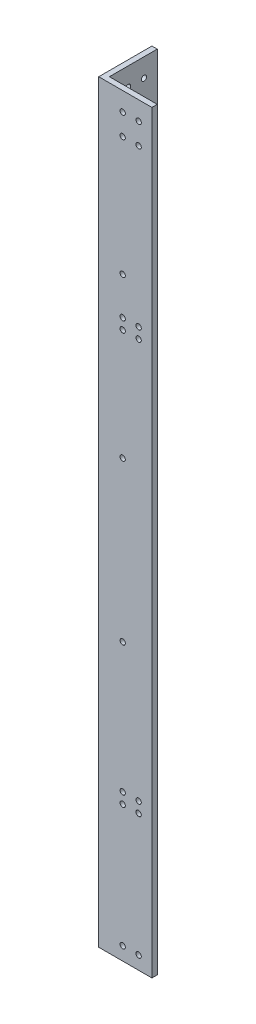
SolidWorks part; units mm, degrees
ref_plane "Front Plane" through (0, 0, 0) normal (0, 0, 1) x (1, 0, 0)
ref_plane "Top Plane" through (0, 0, 0) normal (0, 1, 0) x (1, 0, 0)
ref_plane "Right Plane" through (0, 0, 0) normal (1, 0, 0) x (0, 0, -1)
sketch "Sketch2" plane through (0, 0, 0) normal (0, 1, 0) x (1, 0, 0)
  line L0 (0, 31.75) -> (3.175, 31.75)
  line L1 (3.175, 31.75) -> (3.175, 3.175)
  line L2 (3.175, 3.175) -> (31.75, 3.175)
  line L3 (31.75, 3.175) -> (31.75, 0)
  line L4 (31.75, 0) -> (0, 0)
  line L5 (0, 0) -> (0, 31.75)
  point P9 (1.5875, 31.75)
  point P10 (31.75, 1.5875)
  dimension "D4" = 3.175
  dimension "D1" = 31.75
  dimension "D2" = 31.75
  dimension "D3" = 3.175
extrude "Boss-Extrude1" add sketch "Sketch2" along normal blind 450
sketch "BackSideHoles-Sketch3" plane through (0, 0, 0) normal (0, 0, 1) x (1, 0, 0)
  line L0 (0, 0) -> (31.75, 0) construction
  line L3 (0, 450) -> (0, 0) construction
  circle A0 centre (14.2875, 81.1125) radius 1.5875
  circle A1 centre (23.8125, 81.1125) radius 1.5875
  circle A2 centre (14.2875, 87.4625) radius 1.5875
  circle A3 centre (23.8125, 87.4625) radius 1.5875
  circle A4 centre (14.2875, 438.8875) radius 1.5875
  circle A5 centre (14.2875, 426.1875) radius 1.5875
  circle A6 centre (23.8125, 438.8875) radius 1.5875
  circle A7 centre (23.8125, 426.1875) radius 1.5875
  circle A10 centre (14.2875, 332.6026) radius 1.5875
  circle A11 centre (23.8125, 332.6026) radius 1.5875
  circle A12 centre (14.2875, 326.2526) radius 1.5875
  circle A13 centre (23.8125, 326.2526) radius 1.5875
  circle A14 centre (14.2875, 165) radius 1.5875
  circle A15 centre (14.2875, 260) radius 1.5875
  circle A16 centre (14.2875, 355) radius 1.5875
  circle A17 centre (14.2875, 7.9375) radius 1.5875
  circle A18 centre (23.8125, 7.9375) radius 1.5875
  dimension "D4" = 3.175
  dimension "D1" = 81.1125
  dimension "D2" = 14.2875
  dimension "D8" = 11.1125
  dimension "D5" = 6.35
  dimension "D7" = 6.35
  dimension "D9" = 12.7
  dimension "D3" = 9.525
  dimension "D10" = 332.6026
  dimension "D11" = 165
  dimension "D12" = 95
  dimension "D13" = 95
  dimension "D6" = 7.9375
sketch "RightSideHoles-Sketch4" plane through (0, 0, 0) normal (-1, 0, 0) x (0, 0, 1)
  line L0 (-31.75, 450) -> (0, 450) construction
  line L1 (0, 450) -> (0, 0) construction
  line L3 (-31.75, 0) -> (0, 0) construction
  circle A0 centre (-23.8125, 81.1125) radius 1.5875
  circle A1 centre (-14.2875, 81.1125) radius 1.5875
  circle A2 centre (-23.8125, 87.4625) radius 1.5875
  circle A3 centre (-14.2875, 87.4625) radius 1.5875
  circle A4 centre (-23.8125, 438.8875) radius 1.5875
  circle A5 centre (-14.2875, 438.8875) radius 1.5875
  circle A6 centre (-23.8125, 426.1875) radius 1.5875
  circle A7 centre (-14.2875, 426.1875) radius 1.5875
  circle A10 centre (-23.8125, 332.6026) radius 1.5875
  circle A11 centre (-14.2875, 332.6026) radius 1.5875
  circle A12 centre (-23.8125, 319.9026) radius 1.5875
  circle A13 centre (-14.2875, 319.9026) radius 1.5875
  circle A14 centre (-23.8125, 7.9375) radius 1.5875
  circle A15 centre (-14.2875, 7.9375) radius 1.5875
  circle A16 centre (-14.2875, 165) radius 1.5875
  circle A17 centre (-14.2875, 260) radius 1.5875
  circle A18 centre (-14.2875, 355) radius 1.5875
  dimension "D4" = 3.175
  dimension "D2" = 14.2875
  dimension "D5" = 6.35
  dimension "D9" = 12.7
  dimension "D10" = 332.6026
  dimension "D13" = 95
  dimension "D3" = 81.1125
  dimension "D6" = 11.1125
  dimension "D8" = 7.9375
  dimension "D7" = 12.7
  dimension "D11" = 9.525
  dimension "D12" = 165
  dimension "D14" = 95
extrude "BackSideHoles-Cut-Extrude1" cut sketch "BackSideHoles-Sketch3" against normal blind 3.175
extrude "RightSideHoles-Cut-Extrude2" cut sketch "RightSideHoles-Sketch4" against normal blind 3.175
equation "\"RailThickness\"= .125in'Spec"
equation "\"VSWidth\"= 1.25in'Spec"
equation "\"VSHeight\"= 1.25in'Spec"
equation "\"VSLength\"= 450mm"
equation "\"HoleOffsetFromEdge\"= \"RailThickness\" * 2.5"
equation "\"HoleOffsetFromSide\"= \"RailThickness\" * 3.5"
equation "\"LegHeight\"= 70mm'Space needed for PSU/Stepper/Electronics"
equation "\"VSBottomSideRailHoleY1FromBottomOfLowerRail\"= \"V1 BottomOfLowerRail\" + \"HoleOffsetFromSide\"'Equals 70.1125"
equation "\"VSSideRailHoleX1FromSide\"= \"HoleOffsetFromSide\" + \"RailThickness\""
equation "\"FasteningHoleDiameter\"= .125in"
equation "\"VSBottomSideRailHoleY2FromY1\"= \"LowerRailHeight\" - \"HoleOffsetFromSide\" - \"HoleOffsetFromEdge\"'Equals 6.35"
equation "\"VSTopSideRailHoleY1FromEdge\"= \"HoleOffsetFromEdge\" + \"RailThickness\""
equation "\"D4@BackSideHoles-Sketch3\" = \"FasteningHoleDiameter\""
equation "\"D1@BackSideHoles-Sketch3\" = \"VSBottomSideRailHoleY1FromBottomOfLowerRail\""
equation "\"D2@BackSideHoles-Sketch3\" = \"VSSideRailHoleX1FromSide\""
equation "\"D1@Boss-Extrude1\"=\"VSLength\""
equation "\"D4@RightSideHoles-Sketch4\"=\"FasteningHoleDiameter\""
equation "\"D3@RightSideHoles-Sketch4\" = \"VSBottomSideRailHoleY1FromBottomOfLowerRail\""
equation "\"D2@RightSideHoles-Sketch4\"=\"VSSideRailHoleX1FromSide\""
equation "\"D8@BackSideHoles-Sketch3\" = \"VSTopSideRailHoleY1FromEdge\""
equation "\"D6@RightSideHoles-Sketch4\"=\"VSTopSideRailHoleY1FromEdge\""
equation "\"VSMidSideRailHoleY1FromV8TopOfMidSideRail\"= \"V8 ToTopOfMidSideRail\" - \"HoleOffsetFromEdge\"'Equals 308.2875"
equation "\"LowerRailHeight\"= 1.00in"
equation "\"D2@Sketch2\"=\"VSWidth\""
equation "\"D1@Sketch2\"=\"VSHeight\""
equation "\"MidBackRailHeight\"= 1.00in"
equation "\"VSMidBackRailHoleY1FromV7TopOfMidBackRail\"= \"V7 ToTopOfMidBackRail\" - \"HoleOffsetFromSide\"'Equals 308.2875"
equation "\"TopRailHeight\"= 1.25in"
equation "\"MidSideRailHeight\"= 1.25in"
equation "\"D8@RightSideHoles-Sketch4\"=\"HoleOffsetFromEdge\""
equation "\"D5@BackSideHoles-Sketch3\"=\"VSBottomSideRailHoleY2FromY1\""
equation "\"D5@RightSideHoles-Sketch4\"=\"VSBottomSideRailHoleY2FromY1\""
equation "\"VSMidBackRailHoleY2FromY1\"= \"MidBackRailHeight\" - \"HoleOffsetFromSide\" - \"HoleOffsetFromEdge\"'Equals 6.35"
equation "\"VSMidSideRailHoleY2FromY1\"= \"MidSideRailHeight\" - \"HoleOffsetFromSide\" - \"HoleOffsetFromEdge\"'Equals 12.7"
equation "\"D7@BackSideHoles-Sketch3\"=\"VSMidBackRailHoleY2FromY1\""
equation "\"D9@RightSideHoles-Sketch4\"=\"VSMidSideRailHoleY2FromY1\""
equation "\"VSTopSideRailHoleY2FromY1\"= \"TopRailHeight\" - \"VSTopSideRailHoleY1FromEdge\" - \"HoleOffsetFromEdge\"'Equals 12.7"
equation "\"D9@BackSideHoles-Sketch3\"=\"VSTopSideRailHoleY2FromY1\""
equation "\"VSSideRailHoleX2FromX1\"= \"VSWidth\" - \"VSSideRailHoleX1FromSide\" - \"HoleOffsetFromEdge\""
equation "\"D3@BackSideHoles-Sketch3\"=\"VSSideRailHoleX2FromX1\""
equation "\"D7@RightSideHoles-Sketch4\"=\"VSTopSideRailHoleY2FromY1\""
equation "\"D11@RightSideHoles-Sketch4\"=\"VSSideRailHoleX2FromX1\""
equation "\"V1 BottomOfLowerRail\"= \"LegHeight\""
equation "\"StepperShaftLength\"= 24mm'Pulley will be attached to the end"
equation "\"ZAxisLeadScrewLength\"= 200mm"
equation "\"HotEndToTopOfXAxisGB\"= 63.315144mm'Measured from the100.Should be 63.315144"
equation "\"TopOfGBToBottomOfLinearRail\"= \"LinearGBWidth\" / 2 + \"LinearRailWidth\" / 2"
equation "\"LinearGBWidth\"= 27mm'Spec"
equation "\"V5 ToBottomOfXAxisLinearRail\"= \"V4 ToTopOfBuildPlate/HotEndTip\" + \"HotEndToTopOfXAxisGB\" - \"TopOfGBToBottomOfLinearRail\""
equation "\"LinearRailWidth\"= 12mm'Spec"
equation "\"V6 ToBottomOfGantryPulley\"= \"V5 ToBottomOfXAxisLinearRail\" - \"DistanceFromGABTopToLowerPulley\""
equation "\"GABUpperHeight\"= 6mm"
equation "\"GABMidWallHeight\"= 28mm'Must equal 28 or changes alignment"
equation "\"20TGT2PulleyWidth\"= 8.7mm'The STL of the Pulley in the diagram is a bit larger"
equation "\"GABMidShortRiserHeight\"= \"GABMidWallHeight\" / 2 - \"20TGT2PulleyWidth\"'Equals 5.3"
equation "\"GABRiserBossOffset\"= 0.8mm'Aligns Pulleys"
equation "\"DistanceFromGABTopToLowerPulley\"= \"GABUpperHeight\" + \"GABMidWallHeight\" - \"GABMidShortRiserHeight\" + \"GABRiserBossOffset\" / 2"
equation "\"V7 ToTopOfMidBackRail\"= \"V6 ToBottomOfGantryPulley\" + \"StepperShaftLength\""
equation "\"D10@BackSideHoles-Sketch3\" = \"VSMidBackRailHoleY1FromV7TopOfMidBackRail\""
equation "\"D10@RightSideHoles-Sketch4\"=\"VSMidSideRailHoleY1FromV8TopOfMidSideRail\""
equation "\"BedToBuildPlateStandoffLength\"= 15mm"
equation "\"BuildPlateHeight\"= 8mm'Spec"
equation "\"V4 ToTopOfBuildPlate/HotEndTip\"= \"V2 ToBedAtTopOfZAxis\" + \"BedToBuildPlateStandoffLength\" + \"BuildPlateHeight\""
equation "\"V2 ToBedAtTopOfZAxis\"= \"V1 BottomOfLowerRail\" + \"StepperShaftLength\" + \"ZAxisLeadScrewLength\" - \"LM8UUHeight\" / 2"
equation "\"LM8UUHeight\"= 24mm'Spec"
equation "\"V8 ToTopOfMidSideRail\"= \"V7 ToTopOfMidBackRail\" - \"RailThickness\""
equation "\"VSEnclosureOffsets\"= ( \"VSLength\" - \"LegHeight\" ) / 4"
equation "\"D11@BackSideHoles-Sketch3\"=\"LegHeight\" + \"VSEnclosureOffsets\""
equation "\"D12@BackSideHoles-Sketch3\"=\"VSEnclosureOffsets\""
equation "\"D13@BackSideHoles-Sketch3\"=\"VSEnclosureOffsets\""
equation "\"D12@RightSideHoles-Sketch4\"=\"LegHeight\" + \"VSEnclosureOffsets\""
equation "\"D13@RightSideHoles-Sketch4\"=\"VSEnclosureOffsets\""
equation "\"D14@RightSideHoles-Sketch4\"=\"VSEnclosureOffsets\""
equation "\"D6@BackSideHoles-Sketch3\"=\"HoleOffsetFromEdge\""
